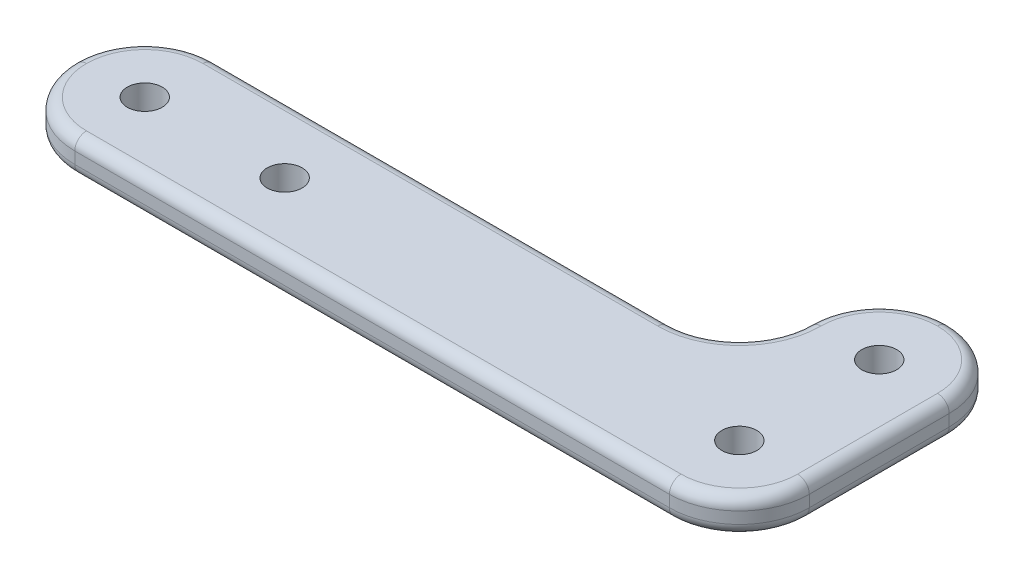
SolidWorks part; units mm, degrees
material "6061 Alloy"
ref_plane "Front Plane" through (0, 0, 0) normal (0, 0, 1) x (1, 0, 0)
ref_plane "Top Plane" through (0, 0, 0) normal (0, 1, 0) x (1, 0, 0)
ref_plane "Right Plane" through (0, 0, 0) normal (1, 0, 0) x (0, 0, -1)
sketch "Sketch1" plane through (0, 0, 0) normal (0, 1, 0) x (1, 0, 0)
  line L0 (0, 25.4) -> (0, -25.4) construction
  line L1 (-12.7, -25.4) -> (12.7, -25.4) construction
  line L2 (-12.7, -25.4) -> (-12.7, 25.4) construction
  line L3 (-12.7, 25.4) -> (12.7, 25.4)
  line L4 (12.7, -25.4) -> (12.7, 25.4) construction
  line L5 (-12.7, -25.4) -> (12.7, 25.4) construction
  line L6 (-12.7, 25.4) -> (12.7, -25.4) construction
  line L7 (-12.7, 0) -> (-120.65, 0)
  line L8 (-120.65, 0) -> (-120.65, -25.4)
  line L9 (-120.65, -25.4) -> (-12.7, -25.4)
  line L10 (-120.65, -12.7) -> (0, -12.7)
  line L11 (-12.7, -25.4) -> (0, -25.4)
  line L12 (12.7, -12.7) -> (12.7, 25.4)
  line L13 (-12.7, 0) -> (-12.7, 25.4)
  circle A1 centre (0, -12.7) radius 3.175
  circle A2 centre (0, 12.7) radius 3.175
  circle A4 centre (0, -12.7) radius 12.7
  circle A5 centre (-107.95, -12.7) radius 3.175
  circle A6 centre (-82.55, -12.7) radius 3.175
  point P0 (0, 0)
  dimension "D3" = 6.35
  dimension "D1" = 25.4
  dimension "D8" = 12.7
  dimension "D6" = 82.55
  dimension "D2" = 25.4
  dimension "D4" = 25.4
  dimension "D5" = 90
  dimension "D7" = 12.7
  dimension "D9" = 25.4
extrude "Boss-Extrude1" add sketch "Sketch1" along normal blind 6.35 contours A5 L10 A4 L12 L3 L13 L7 L8 A2 | A4 A1 | A5 L10 L8 L9 L11 A4 region at (-43.7152, 0, 0.3715) region at (8.7263, 0, 21.4263) region at (-64.5851, 0, 19.2538)
fillet "Fillet2" radius 12.7 5 edges at (12.7, 3.175, -25.4) (-12.7, 3.175, -25.4) (-120.65, 3.175, 0) (-120.65, 3.175, 25.4) (-12.7, 3.175, 0)
fillet "Fillet3" radius 2.1167 18 edges at (-8.9803, 0, -21.6803) (8.9803, 0, -21.6803) (12.7, 0, 0) (8.9803, 0, 21.6803) (-53.975, 0, 25.4) (-116.9303, 0, 21.6803) (-116.9303, 0, 3.7197) (-8.9803, 6.35, -21.6803) (8.9803, 6.35, -21.6803) (12.7, 6.35, 0) (8.9803, 6.35, 21.6803) (-53.975, 6.35, 25.4) (-116.9303, 6.35, 21.6803) (-116.9303, 6.35, 3.7197) (-66.675, 0, 0) (-66.675, 6.35, 0) (-16.4197, 0, -3.7197) (-16.4197, 6.35, -3.7197)
